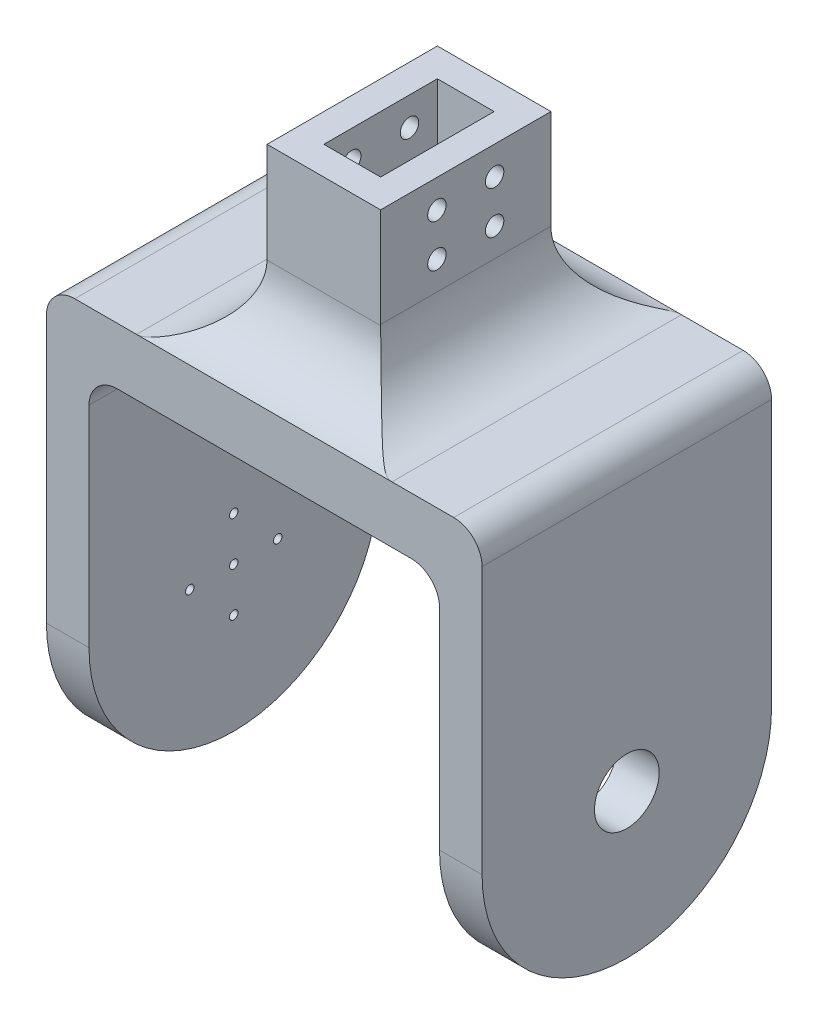
SolidWorks part; units mm, degrees
ref_plane "Alzado" through (0, 0, 0) normal (0, 0, 1) x (1, 0, 0)
ref_plane "Planta" through (0, 0, 0) normal (0, 1, 0) x (1, 0, 0)
ref_plane "Vista lateral" through (0, 0, 0) normal (1, 0, 0) x (0, 0, -1)
sketch "Croquis1" plane through (0, 0, 0) normal (0, 0, 1) x (1, 0, 0)
  line L0 (0, 0) -> (0, 46.6425) construction
  line L2 (-61.75, 0) -> (-76.75, 0)
  line L3 (-61.75, 0) -> (-61.75, 125)
  line L5 (-76.75, 0) -> (-76.75, 145)
  line L6 (-51.75, 135) -> (51.75, 135)
  line L8 (-66.75, 155) -> (66.75, 155)
  line L12 (0, 135) -> (-51.75, 135)
  line L15 (76.75, 0) -> (76.75, 145)
  line L16 (61.75, 0) -> (61.75, 125)
  line L17 (61.75, 0) -> (76.75, 0)
  arc A0 (-66.75, 155) -> (-76.75, 145) centre (-66.75, 145) ccw
  arc A1 (-61.75, 125) -> (-51.75, 135) centre (-51.75, 125) cw
  arc A2 (61.75, 125) -> (51.75, 135) centre (51.75, 125) ccw
  arc A3 (66.75, 155) -> (76.75, 145) centre (66.75, 145) cw
  point P5 (0, 106.1603)
  point P23 (0, 208)
  dimension "D5" = 10
  dimension "D6" = 155
  dimension "D1" = 135
  dimension "D2" = 61.75
  dimension "D3" = 15
extrude "Saliente-Extruir1" add sketch "Croquis1" along normal blind 102 contours A3 L8 A0 L5 L2 L3 A1 L6 A2 L16 L17 L15 region at (-69.25, 2.1815, 0)
sketch "Croquis2" plane through (-76.75, 0, 0) normal (-1, 0, 0) x (0, 0, 1)
  line L1 (102, 0) -> (0, 0) construction
  line L2 (0, 51) -> (102, 51)
  arc A0 (0, 51) -> (102, 51) centre (51, 51) ccw
  point P4 (51, 0)
  line M1 (0, 145) -> (0, 0)
  line M2 (0, 0) -> (102, 0)
  line M3 (102, 0) -> (102, 145)
  dimension "D1" = 102
extrude "Cortar-Extruir1" cut sketch "Croquis2" against normal through all contours A0 M1 M2 | A0 M2 M3 region at (-76.75, 11.3918, 11.3918) region at (-76.75, 11.3918, 90.6082)
sketch "Croquis3" plane through (-76.75, 0, 0) normal (-1, 0, 0) x (0, 0, 1)
  circle A0 centre (51, 51) radius 1.5
  circle A1 centre (51, 66.5) radius 1.5
  circle A2 centre (51, 66.5) radius 3
  circle A3 centre (66.5, 51) radius 3
  circle A4 centre (66.5, 51) radius 1.5
  circle A5 centre (51, 35.5) radius 3
  circle A6 centre (51, 35.5) radius 1.5
  circle A7 centre (35.5, 51) radius 3
  circle A8 centre (35.5, 51) radius 1.5
  dimension "D1" = 3
  dimension "D2" = 6
  dimension "D3" = 3
  dimension "D4" = 15.5
  dimension "D5" = 4
extrude "Cortar-Extruir2" cut sketch "Croquis3" against normal blind 30 contours A8 | A1 | A4 | A0 | A6 region at (-76.75, 51, 51) region at (-76.75, 66.5, 51) region at (-76.75, 51, 66.5) region at (-76.75, 35.5, 51) region at (-76.75, 51, 35.5)
extrude "Cortar-Extruir3" cut sketch "Croquis3<3>" against normal blind 5 contours A7 A8 | A2 A1 | A3 A4 | A5 A6 region at (-76.75, 66.5, 48.0849) region at (-76.75, 51, 63.5849) region at (-76.75, 35.5, 48.0849) region at (-76.75, 51, 32.5849)
sketch "Croquis3<3>" plane through (-76.75, 0, 0) normal (-1, 0, 0) x (0, 0, 1) same geometry as "Croquis3"
chamfer "Chaflán1" distance 0.4 angle 45 4 edges at (-76.75, 35.5, 54) (-76.75, 51, 69.5) (-76.75, 66.5, 54) (-76.75, 51, 38.5)
sketch "Croquis5" plane through (76.75, 0, 0) normal (1, 0, 0) x (0, 0, -1)
  circle A1 centre (-51, 51) radius 11.4
  dimension "D1" = 22.8
extrude "Cortar-Extruir4" cut sketch "Croquis5" against normal blind 30
sketch "Croquis6" plane through (0, 155, 0) normal (0, 1, 0) x (1, 0, 0)
  line L1 (-10, -31) -> (10, -31)
  line L2 (-10, -31) -> (-10, -71)
  line L3 (-10, -71) -> (10, -71)
  line L4 (10, -31) -> (10, -71)
  line L5 (-10, -31) -> (10, -71) construction
  line L6 (-10, -71) -> (10, -31) construction
  line L10 (-66.75, -102) -> (66.75, -102) construction
  line L11 (-20, -21) -> (20, -21)
  line L12 (20, -21) -> (20, -81)
  line L13 (-20, -81) -> (20, -81)
  line L14 (-20, -21) -> (-20, -81)
  point P0 (0, -51)
  dimension "D1" = 51
  dimension "D2" = 40
  dimension "D3" = 20
  dimension "D4" = 10
extrude "Saliente-Extruir2" add sketch "Croquis6" along normal blind 60
fillet "Redondeo2" radius 25 4 edges at (0, 155, 21) (-20, 155, 51) (0, 155, 81) (20, 155, 51)
sketch "Croquis7" plane through (-20, 0, 0) normal (-1, 0, 0) x (0, 0, 1)
  line L0 (21, 215) -> (21, 180) construction
  line L1 (21, 215) -> (81, 215) construction
  line L2 (51, 215) -> (51, 146.5068) construction
  line L3 (21, 197.5) -> (76.7585, 197.5) construction
  circle A0 centre (40.8348, 205) radius 3.25
  circle A1 centre (61.1652, 205) radius 3.25
  circle A2 centre (61.1652, 190) radius 3.25
  circle A3 centre (40.8348, 190) radius 3.25
  dimension "D2" = 6.5
  dimension "D1" = 19.8348
  dimension "D3" = 10
extrude "Cortar-Extruir5" cut sketch "Croquis7" against normal through all
